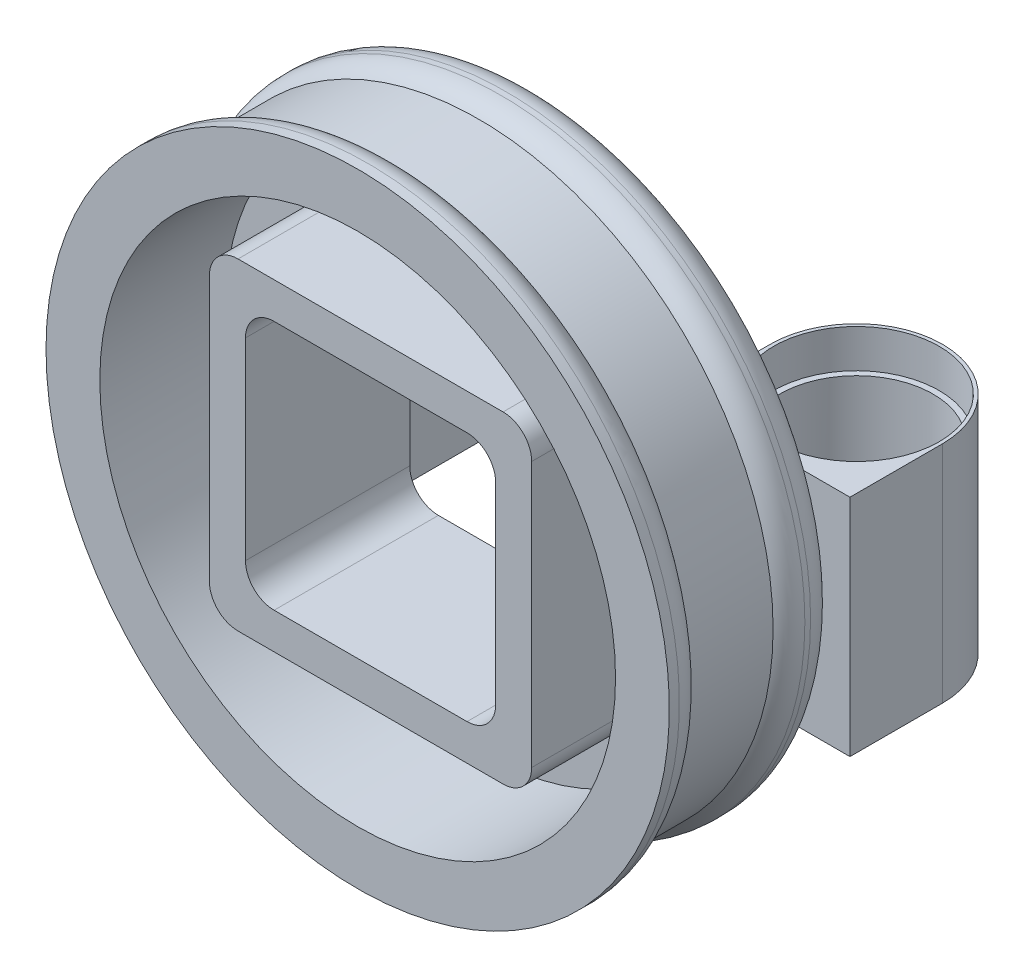
SolidWorks part; units mm, degrees
ref_plane "Front Plane" through (0, 0, 0) normal (0, 0, 1) x (1, 0, 0)
ref_plane "Top Plane" through (0, 0, 0) normal (0, 1, 0) x (1, 0, 0)
ref_plane "Right Plane" through (0, 0, 0) normal (1, 0, 0) x (0, 0, -1)
sketch "Sketch1" plane through (0, 0, 0) normal (0, 1, 0) x (1, 0, 0)
  line L0 (0, 20.7727) -> (0, -26.7463) construction
  line L1 (0, 5.74) -> (10.635, 5.74)
  line L2 (10.635, 5.74) -> (10.635, 3.78)
  line L3 (10.635, 3.78) -> (10.285, 3.78)
  line L4 (10.285, 3.78) -> (10.285, 0.82)
  line L5 (10.285, 0.82) -> (10.89, 0.82)
  line L6 (10.89, 0.82) -> (10.89, -0.45)
  line L7 (10.89, -0.45) -> (9.01, -0.45)
  line L8 (9.01, -0.45) -> (9.01, 0)
  line L9 (9.01, 0) -> (0, 0)
  line L10 (0, 0) -> (0, 5.74)
  dimension "D1" = 10.635
  dimension "D2" = 10.89
  dimension "D3" = 0.35
  dimension "D4" = 1.27
  dimension "D5" = 9.01
  dimension "D6" = 5.74
  dimension "D7" = 2.96
  dimension "D8" = 1.96
revolve "Revolve1" add sketch "Sketch1" angle 360 about L0
fillet "Fillet3" radius 1 3 edges at (-10.635, 0, -3.78) (-10.635, 0, -5.74) (-10.89, 0, -0.82)
sketch "Sketch13" plane through (0, 0, 0) normal (0, 0, 1) x (1, 0, 0)
  line L0 (-5.63, 5.63) -> (5.63, 5.63)
  line L1 (-4.38, -4.38) -> (4.38, -4.38)
  line L2 (-4.38, -4.38) -> (-4.38, 4.38)
  line L3 (-4.38, 4.38) -> (4.38, 4.38)
  line L4 (4.38, -4.38) -> (4.38, 4.38)
  line L5 (-4.38, -4.38) -> (4.38, 4.38) construction
  line L6 (-4.38, 4.38) -> (4.38, -4.38) construction
  line L7 (5.63, -5.63) -> (5.63, 5.63)
  line L8 (-5.63, -5.63) -> (5.63, -5.63)
  line L9 (-5.63, -5.63) -> (-5.63, 5.63)
  line L10 (-5.63, 5.63) -> (-5.63, 7.0344)
  line L11 (-5.63, -5.63) -> (-5.63, -7.0344)
  line L12 (5.63, -5.63) -> (5.63, -7.0344)
  line L13 (5.63, 5.63) -> (5.63, 7.0344)
  circle A2 centre (0, 0) radius 9.01 construction
  circle A3 centre (0, 0) radius 9.01 construction
  point P0 (0, 0)
  circle M5 centre (0, 0) radius 9.01
  dimension "D1" = 8.76
  dimension "D2" = 1.25
extrude "Cut-Extrude6" cut sketch "Sketch13" against normal blind 3.94 contours L11 L9 L10 M5 | L12 L8 L11 M5 | L13 L7 L12 M5 | L0 L13 L10 M5 region at (0, 7.0673, 0) region at (-7.0064, 0, 0) region at (7.0064, 0, 0) region at (0, -7.0673, 0)
fillet "Fillet5" radius 1 4 edges at (5.63, -5.63, -1.97) (5.63, 5.63, -1.97) (-5.63, 5.63, -1.97) (-5.63, -5.63, -1.97)
sketch3d "3DSketch1"
  line L0 (-4.37, -4.37, 0) -> (4.37, -4.37, 0)
  line L1 (4.37, -4.37, 0) -> (4.37, 4.37, 0)
  line L2 (4.37, 4.37, 0) -> (-4.37, 4.37, 0)
  line L3 (-4.37, 4.37, 0) -> (-4.37, -4.37, 0)
  line L4 (-3.37, -4.37, 0) -> (3.37, -4.37, 0)
  line L5 (4.37, -3.37, 0) -> (4.37, 3.37, 0)
  line L6 (3.37, 4.37, 0) -> (-3.37, 4.37, 0)
  line L7 (-4.37, 3.37, 0) -> (-4.37, -3.37, 0)
  arc A0 (-3.37, -4.37, 0) -> (-4.37, -3.37, 0) centre (-3.37, -3.37, 0) ccw
  arc A1 (3.37, -4.37, 0) -> (4.37, -3.37, 0) centre (3.37, -3.37, 0) ccw
  arc A2 (4.37, 3.37, 0) -> (3.37, 4.37, 0) centre (3.37, 3.37, 0) ccw
  arc A3 (-3.37, 4.37, 0) -> (-4.37, 3.37, 0) centre (-3.37, 3.37, 0) ccw
  point P6 (-4.37, -4.37, 0)
  point P8 (-3.37, -3.37, -1)
  point P11 (4.37, -4.37, 0)
  point P13 (3.37, -3.37, 1)
  point P16 (4.37, 4.37, 0)
  point P18 (3.37, 3.37, 1)
  point P21 (-4.37, 4.37, 0)
  point P23 (-3.37, 3.37, 1)
  dimension "D2" = 1
  dimension "D1" = 1.26
extrude "Cut-Extrude7" cut sketch "3DSketch1" along direction (0, 0, -1) on the side of the normal blind 10.94
sketch "Sketch14" plane through (0, 0, -5.74) normal (0, 0, -1) x (-1, 0, 0)
  line L0 (0, 9.635) -> (0, -9.635) construction
  line L1 (-4.37, 3.37) -> (-11.63, 3.37)
  line L2 (-4.37, 3.37) -> (-4.37, -4.48)
  line L3 (-4.37, -4.48) -> (-11.63, -4.48)
  line L4 (-11.63, 3.37) -> (-11.63, -4.48)
  line L5 (4.37, 3.37) -> (4.37, -4.48)
  line L6 (4.37, -4.48) -> (11.63, -4.48)
  line L7 (11.63, 3.37) -> (11.63, -4.48)
  line L8 (4.37, 3.37) -> (11.63, 3.37)
  circle A0 centre (0, 0) radius 9.635 construction
  dimension "D1" = 7.26
  dimension "D2" = 7.85
extrude "Boss-Extrude2" add sketch "Sketch14" along normal blind 6.47
sketch "Sketch15" plane through (0, -4.48, 0) normal (0, -1, 0) x (1, 0, 0)
  line L0 (0, 2.554) -> (0, -10.6006) construction
sketch "Sketch16" plane through (0, -4.48, 0) normal (0, -1, 0) x (1, 0, 0)
  line L0 (-11.01, -8.975) -> (-11.01, -5.74)
  line L1 (-8.5301, -5.74) -> (-11.63, -5.74) construction
  line L2 (-4.99, -8.975) -> (-4.99, -5.74)
  line L3 (-4.37, -5.74) -> (-8.5301, -5.74) construction
  line L4 (-11.63, -8.975) -> (-4.37, -8.975) construction
  line L5 (4.99, -8.975) -> (4.99, -5.74)
  line L6 (-4.37, -5.74) -> (-11.63, -5.74)
  line L7 (-4.37, -5.74) -> (-4.37, -12.21)
  line L8 (0, 0) -> (0, -14.5168) construction
  line L9 (-11.63, -12.21) -> (-11.63, -5.74) construction
  line L10 (-4.37, -12.21) -> (-4.37, -5.74) construction
  line L11 (-4.37, -12.21) -> (-11.63, -12.21)
  line L12 (-11.63, -5.74) -> (-11.63, -12.21)
  line L13 (4.37, -5.74) -> (11.63, -5.74)
  line L14 (11.01, -8.975) -> (11.01, -5.74)
  line L15 (11.63, -5.74) -> (11.63, -12.21)
  line L16 (4.37, -12.21) -> (11.63, -12.21)
  line L17 (4.37, -5.74) -> (4.37, -12.21)
  circle A0 centre (-8, -8.975) radius 3.01
  circle A1 centre (8, -8.975) radius 3.01
  point P10 (-8, -8.975)
  line M1 (11.63, -5.74) -> (8.5301, -5.74)
  line M2 (8.5301, -5.74) -> (4.37, -5.74)
  line M3 (4.37, -5.74) -> (4.37, -12.21)
  line M4 (4.37, -12.21) -> (11.63, -12.21)
  line M5 (11.63, -12.21) -> (11.63, -5.74)
  dimension "D1" = 6.02
extrude "Cut-Extrude16" cut sketch "Sketch16" against normal blind 16.47 contours A0 L0 L6 L12 L11 L7 L2 | L14 A1 L5 M2 M3 M4 M5 M1 region at (-8, -4.48, -12.0822) region at (8, -4.48, -12.0822)
sketch "Sketch19" plane through (0, 3.37, 0) normal (0, 1, 0) x (1, 0, 0)
  line L0 (0, 0) -> (0, 6.7337) construction
  circle A0 centre (-8, 8.975) radius 2.68
  circle A2 centre (-8, 8.975) radius 2.8918
  circle A4 centre (8, 8.975) radius 2.8918
  circle A5 centre (8, 8.975) radius 2.68
  dimension "D1" = 5.36
  dimension "D2" = 5.7837
extrude "Cut-Extrude20" cut sketch "Sketch19" against normal blind 1.34
sketch "Sketch21" plane through (0, -4.48, 0) normal (0, -1, 0) x (1, 0, 0)
  line L0 (0, 0) -> (0, -11.0573) construction
  circle A0 centre (-8, -8.975) radius 2.89
  circle A1 centre (-8, -8.975) radius 2.68
  circle A2 centre (8, -8.975) radius 2.68
  circle A3 centre (8, -8.975) radius 2.89
  dimension "D1" = 5.78
  dimension "D2" = 5.36
extrude "Cut-Extrude21" cut sketch "Sketch21" against normal blind 1.34
sketch "Sketch22" plane through (0, 3.37, 0) normal (0, 1, 0) x (1, 0, 0)
  line L0 (0, 0) -> (0, 12.1316) construction
sketch "Sketch23" plane through (0, 3.37, 0) normal (0, 1, 0) x (1, 0, 0)
  line L0 (0, 0) -> (0, -4.3597) construction
  circle A0 centre (-8, 8.975) radius 2.68
  circle A1 centre (-8, 8.975) radius 2.68 construction
  circle A2 centre (8, 8.975) radius 2.68
extrude "Cut-Extrude22" cut sketch "Sketch23" against normal blind 21.34
